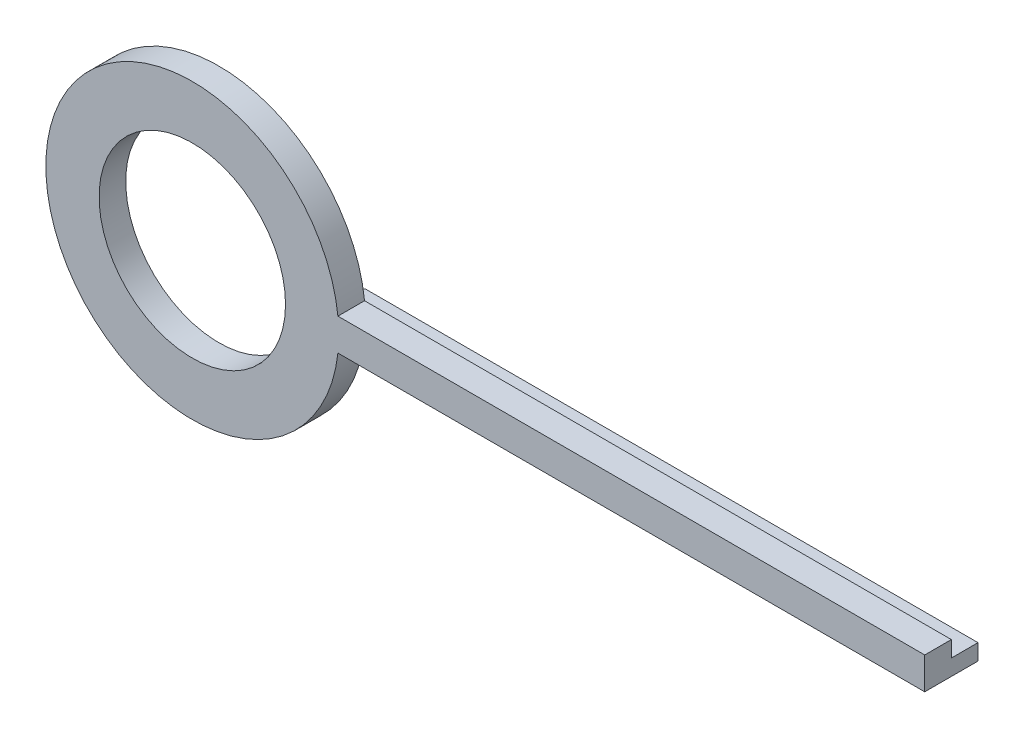
SolidWorks part; units mm, degrees
ref_plane "Front Plane" through (0, 0, 0) normal (0, 0, 1) x (1, 0, 0)
ref_plane "Top Plane" through (0, 0, 0) normal (0, 1, 0) x (1, 0, 0)
ref_plane "Right Plane" through (0, 0, 0) normal (1, 0, 0) x (0, 0, -1)
sketch "Sketch1" plane through (0, 0, 0) normal (0, 0, 1) x (1, 0, 0)
  circle A0 centre (0, 0) radius 27.5
  circle A1 centre (0, 0) radius 17.5
  dimension "D1" = 35
  dimension "D2" = 10
extrude "Boss-Extrude1" add sketch "Sketch1" along normal blind 5
sketch "Sketch2" plane through (0, 0, 5) normal (0, 0, 1) x (1, 0, 0)
  line L1 (17.5, 3) -> (137.5, 3)
  line L2 (17.5, 3) -> (17.5, -3)
  line L3 (17.5, -3) -> (137.5, -3)
  line L4 (137.5, 3) -> (137.5, -3)
  circle A0 centre (0, 0) radius 17.5 construction
  dimension "D1" = 3
  dimension "D2" = 3
  dimension "D3" = 17.5
  dimension "D4" = 120
extrude "Boss-Extrude2" add sketch "Sketch2" against normal blind 10
sketch "Sketch3" plane through (17.5, 0, 0) normal (-1, 0, 0) x (0, 0, 1)
  line L1 (-5, 3) -> (0, 3)
  line L2 (-5, 3) -> (-5, 0)
  line L3 (-5, 0) -> (0, 0)
  line L4 (0, 3) -> (0, 0)
extrude "Cut-Extrude1" cut sketch "Sketch3" against normal blind 140
chamfer "Chamfer1" distance 5 angle 45 1 edges at (17.5, -1.5, -5)
